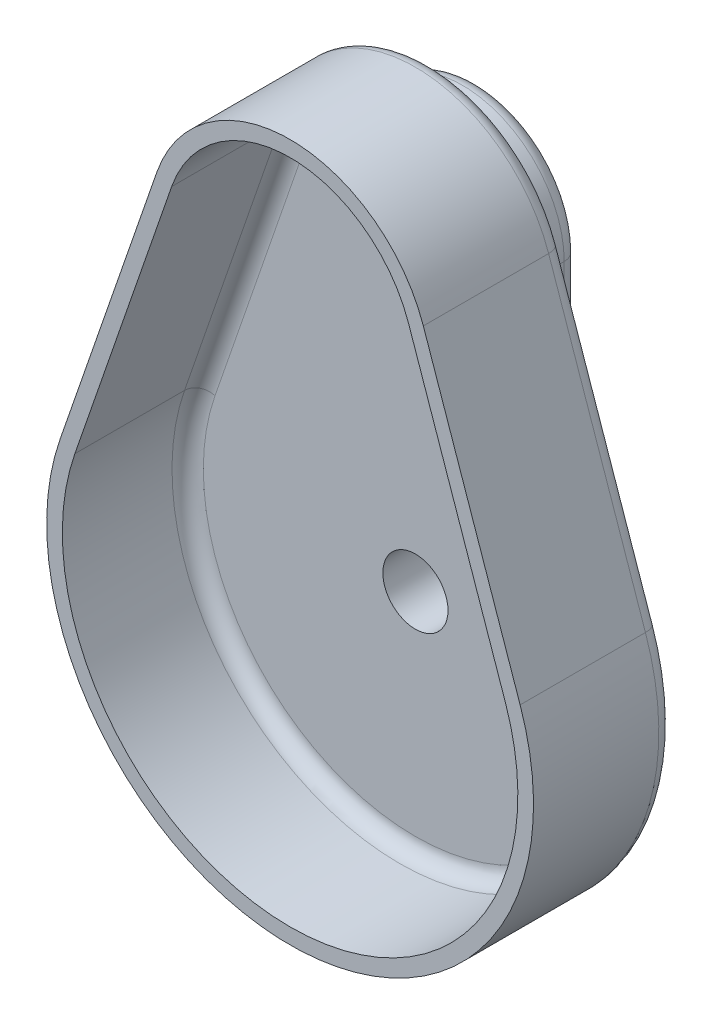
SolidWorks part; units mm, degrees
ref_plane "Front Plane" through (0, 0, 0) normal (0, 0, 1) x (1, 0, 0)
ref_plane "Top Plane" through (0, 0, 0) normal (0, 1, 0) x (1, 0, 0)
ref_plane "Right Plane" through (0, 0, 0) normal (1, 0, 0) x (0, 0, -1)
sketch "Sketch1" plane through (0, 0, 0) normal (0, 0, 1) x (1, 0, 0)
  line L0 (0, 31.75) -> (0, 0) construction
  line L1 (10.3187, 31.75) -> (10.3187, 0)
  line L2 (-10.3187, 31.75) -> (-10.3187, 0)
  circle A0 centre (0, 0) radius 3.302
  circle A1 centre (0, 31.75) radius 3.302
  arc A2 (10.3187, 31.75) -> (-10.3187, 31.75) centre (0, 31.75) ccw
  arc A3 (-10.3187, 0) -> (10.3187, 0) centre (0, 0) ccw
  point P5 (0, 15.875)
  dimension "D1" = 6.604
  dimension "D2" = 6.604
  dimension "D4" = 10.3187
  dimension "D3" = 31.75
extrude "Boss-Extrude1" add sketch "Sketch1" along normal blind 6.35
sketch "Sketch2" plane through (0, 0, 0) normal (0, 0, -1) x (-1, 0, 0)
  line L0 (-23.3135, 8.067) -> (-13.502, 36.422)
  line L1 (23.3135, 8.067) -> (13.502, 36.422)
  arc A0 (13.502, 36.422) -> (-13.502, 36.422) centre (0, 31.75) ccw
  arc A1 (-23.3135, 8.067) -> (23.3135, 8.067) centre (0, 0) ccw
  circle A3 centre (0, 0) radius 3.302
  circle A4 centre (0, 0) radius 3.302
  circle A5 centre (0, 31.75) radius 3.302
  circle A6 centre (0, 31.75) radius 3.302
  circle A7 centre (0, 0) radius 22.225 construction
  circle A8 centre (0, 31.75) radius 11.1125 construction
  dimension "D1" = 49.3395
  dimension "D2" = 28.575
  dimension "D5" = 44.45
  dimension "D6" = 22.225
  dimension "D3" = 0
  dimension "D4" = 0
extrude "Boss-Extrude2" add sketch "Sketch2" along normal blind 1.5875 from surface starting at face at (3.302, 0, 6.35)
sketch "Sketch3" plane through (0, 0, 6.35) normal (0, 0, 1) x (1, 0, 0)
  line L0 (21.8133, 7.5479) -> (12.0018, 35.9029)
  line L1 (-12.0018, 35.9029) -> (-21.8133, 7.5479)
  line L2 (-13.502, 36.422) -> (-23.3135, 8.067)
  line L3 (23.3135, 8.067) -> (13.502, 36.422)
  line L4 (-13.502, 36.422) -> (-23.3135, 8.067)
  line L5 (23.3135, 8.067) -> (13.502, 36.422)
  arc A0 (-21.8133, 7.5479) -> (21.8133, 7.5479) centre (0, 0) ccw
  arc A1 (12.0018, 35.9029) -> (-12.0018, 35.9029) centre (0, 31.75) ccw
  arc A2 (13.502, 36.422) -> (-13.502, 36.422) centre (0, 31.75) ccw
  arc A3 (-23.3135, 8.067) -> (23.3135, 8.067) centre (0, 0) ccw
  arc A4 (13.502, 36.422) -> (-13.502, 36.422) centre (0, 31.75) ccw
  arc A5 (-23.3135, 8.067) -> (23.3135, 8.067) centre (0, 0) ccw
  dimension "D1" = 0
  dimension "D2" = 1.5875
extrude "Boss-Extrude3" add sketch "Sketch3" along normal blind 12.7
fillet "Fillet1" radius 1.5875 12 edges at (-16.9075, 21.7254, 6.35) (0, 44.45, 6.35) (16.9075, 21.7254, 6.35) (-18.4078, 22.2445, 4.7625) (0, 46.0375, 4.7625) (18.4078, 22.2445, 4.7625) (0, -10.3187, 4.7625) (-10.3187, 15.875, 4.7625) (0, 42.0687, 4.7625) (0, -23.0822, 6.35) (0, -24.6697, 4.7625) (10.3187, 15.875, 4.7625)
fillet "Fillet2" radius 1.5875 4 edges at (-10.3187, 15.875, 0) (0, 42.0687, 0) (10.3187, 15.875, 0) (0, -10.3187, 0)
